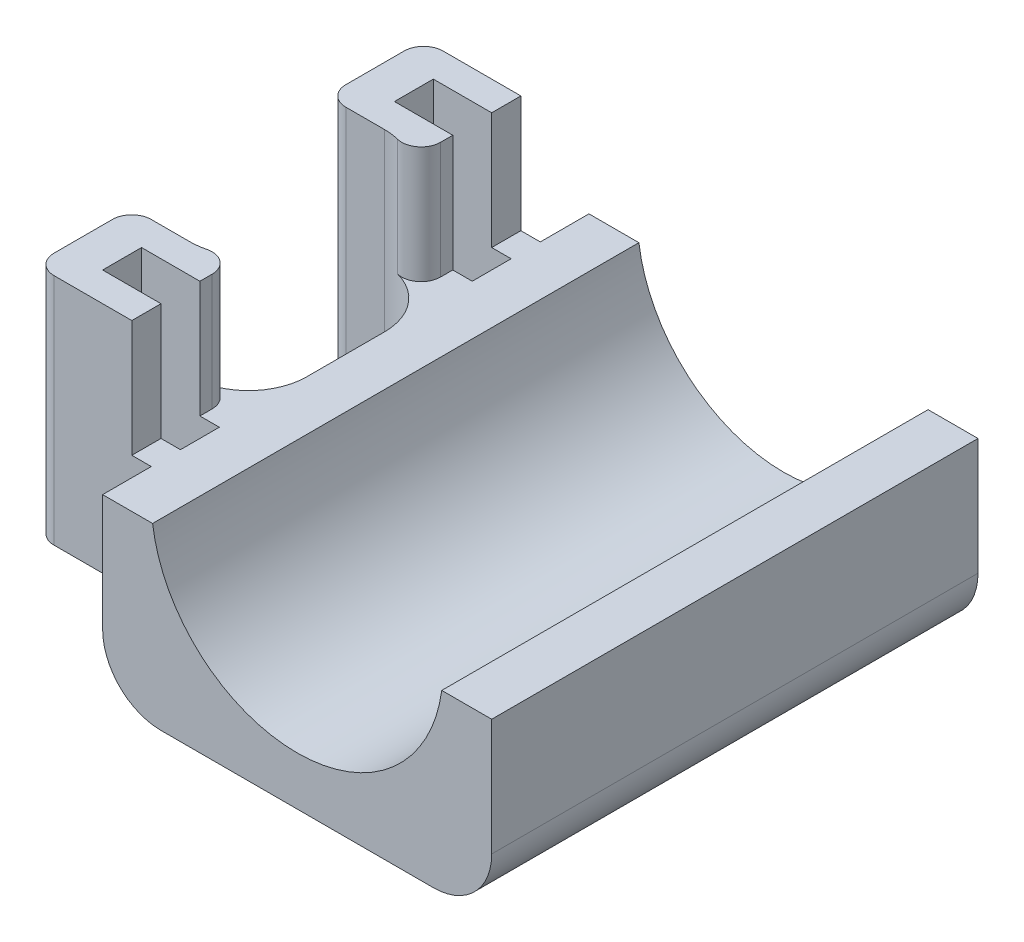
SolidWorks part; units mm, degrees
ref_plane "Plano frontal" through (0, 0, 0) normal (0, 0, 1) x (1, 0, 0)
ref_plane "Plano superior" through (0, 0, 0) normal (0, 1, 0) x (1, 0, 0)
ref_plane "Plano direito" through (0, 0, 0) normal (1, 0, 0) x (0, 0, -1)
sketch "Esboço1" plane through (0, 0, 0) normal (0, 1, 0) x (1, 0, 0)
  line L1 (-10, 12.5) -> (10, 12.5)
  line L2 (-10, 12.5) -> (-10, -12.5)
  line L3 (-10, -12.5) -> (10, -12.5)
  line L4 (10, 12.5) -> (10, -12.5)
  line L5 (-10, 12.5) -> (10, -12.5) construction
  line L6 (-10, -12.5) -> (10, 12.5) construction
  point P0 (0, 0)
  dimension "D1" = 20
  dimension "D2" = 25
extrude "Ressalto-extrusão1" add sketch "Esboço1" along normal blind 9
sketch "Esboço2" plane through (0, 0, 12.5) normal (0, 0, 1) x (1, 0, 0)
  line L0 (-10, 9) -> (10, 9) construction
  circle A0 centre (0, 10) radius 7.5
  dimension "D2" = 15
  dimension "D1" = 1
extrude "Corte-extrusão1" cut sketch "Esboço2" against normal through all
fillet "Filete1" radius 3 2 edges at (10, 0, 0) (-10, 0, 0)
sketch "Esboço3" plane through (0, 9, 0) normal (0, 1, 0) x (1, 0, 0)
  line L0 (-16, 10) -> (-10, 5) construction
  line L5 (-10, 12.5) -> (-10, -12.5) construction
  line L10 (-9.5, -5) -> (-16.5, -10) construction
  line L15 (-16, 10) -> (-10, 10)
  line L16 (-16, 10) -> (-16, 5)
  line L17 (-16, 5) -> (-10, 5)
  line L18 (-10, 10) -> (-10, 8.5)
  line L19 (-13, 7.5) -> (-13, -7.5) construction
  line L20 (-10, 6.5) -> (-10, 5)
  line L21 (-14, 8.5) -> (-10, 8.5)
  line L22 (-14, 8.5) -> (-14, 6.5)
  line L23 (-14, 6.5) -> (-10, 6.5)
  line L25 (0, 0) -> (-10, 0) construction
  line L26 (-14, -6.5) -> (-10, -6.5)
  line L27 (-14, -8.5) -> (-14, -6.5)
  line L28 (-14, -8.5) -> (-10, -8.5)
  line L29 (-10, -6.5) -> (-10, -5)
  line L30 (-10, -10) -> (-10, -8.5)
  line L31 (-16, -5) -> (-10, -5)
  line L32 (-16, -10) -> (-16, -5)
  line L33 (-16, -10) -> (-10, -10)
  point P14 (-13, 0)
  point P22 (-14, 7.5)
  dimension "D1" = 15
  dimension "D2" = 6
  dimension "D3" = 5
  dimension "D4" = 4
  dimension "D5" = 2
extrude "Ressalto-extrusão2" add sketch "Esboço3" against normal blind 6
sketch "Esboço4" plane through (0, 9, 0) normal (0, 1, 0) x (1, 0, 0)
  line L0 (-16, -10) -> (-16, -5)
  line L1 (-16, -5) -> (-11, -5)
  line L2 (-10, -5) -> (-16, -5) construction
  line L3 (-11, -5) -> (-11, -6.5)
  line L4 (-14, -6.5) -> (-10, -6.5) construction
  line L5 (-11, -6.5) -> (-14, -6.5)
  line L6 (-14, -6.5) -> (-14, -8.5)
  line L7 (-14, -8.5) -> (-11, -8.5)
  line L8 (-10, -8.5) -> (-14, -8.5) construction
  line L9 (-11, -8.5) -> (-11, -10)
  line L10 (-16, -10) -> (-10, -10) construction
  line L11 (-11, -10) -> (-16, -10)
  line L12 (-10, 5) -> (-10, -5) construction
  line L13 (0, 0) -> (-10, 0) construction
  line L14 (-11, 10) -> (-16, 10)
  line L15 (-11, 8.5) -> (-11, 10)
  line L16 (-14, 8.5) -> (-11, 8.5)
  line L17 (-14, 6.5) -> (-14, 8.5)
  line L18 (-11, 6.5) -> (-14, 6.5)
  line L19 (-11, 5) -> (-11, 6.5)
  line L20 (-16, 5) -> (-11, 5)
  line L21 (-16, 10) -> (-16, 5)
  dimension "D1" = 1
extrude "Ressalto-extrusão3" add sketch "Esboço4" along normal blind 6
fillet "Filete3" radius 1 4 edges at (-16, 9, -10) (-16, 9, -5) (-16, 9, 5) (-16, 9, 10)
fillet "Filete5" radius 3 2 edges at (-10, 6, -5) (-10, 6, 5)
fillet "Filete6" radius 1 2 edges at (-11, 12, -4.2361) (-11, 12, 4.2361)
